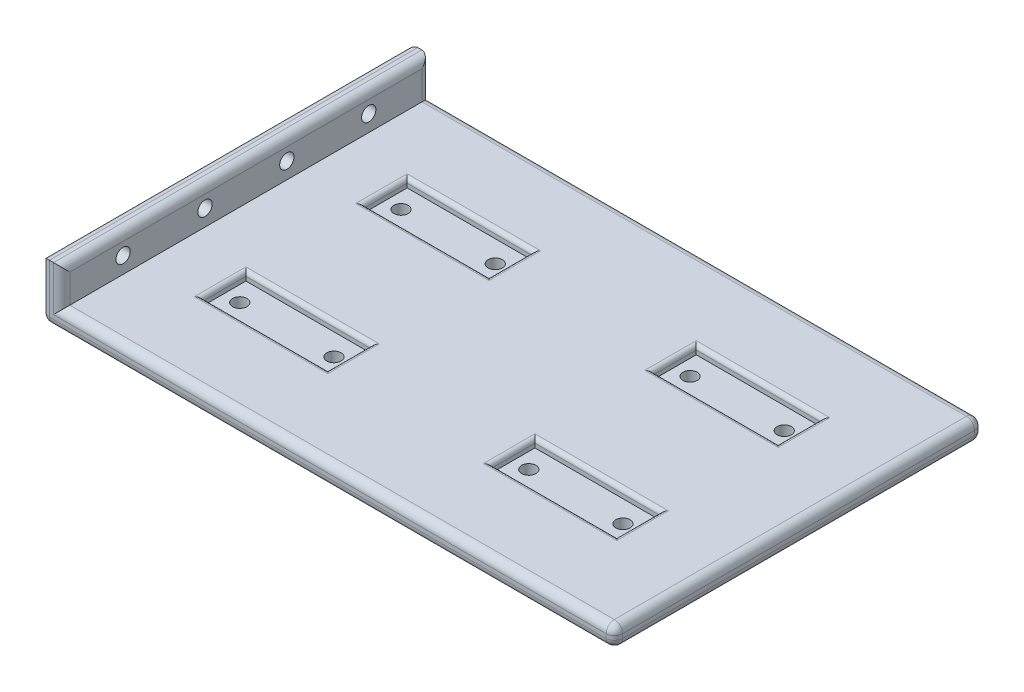
SolidWorks part; units mm, degrees
ref_plane "正面" through (0, 0, 0) normal (0, 0, 1) x (1, 0, 0)
ref_plane "平面" through (0, 0, 0) normal (0, 1, 0) x (1, 0, 0)
ref_plane "右側面" through (0, 0, 0) normal (1, 0, 0) x (0, 0, -1)
sketch "ｽｹｯﾁ1" plane through (0, 0, 0) normal (0, 1, 0) x (1, 0, 0)
  line L1 (-70, 45) -> (70, 45)
  line L2 (-70, 45) -> (-70, -45)
  line L3 (-70, -45) -> (70, -45)
  line L4 (70, 45) -> (70, -45)
  line L5 (-70, 45) -> (70, -45) construction
  line L6 (-70, -45) -> (70, 45) construction
  point P0 (0, 0)
extrude "ﾎﾞｽ - 押し出し1" add sketch "ｽｹｯﾁ1" along normal blind 5
sketch "ｽｹｯﾁ2" plane through (0, 5, 0) normal (0, 1, 0) x (1, 0, 0)
  line L1 (-70, 45) -> (-65, 45)
  line L2 (-70, 45) -> (-70, -45)
  line L3 (-70, -45) -> (-65, -45)
  line L4 (-65, 45) -> (-65, -45)
  dimension "D1" = 5
extrude "ﾎﾞｽ - 押し出し2" add sketch "ｽｹｯﾁ2" along normal blind 9
sketch "ｽｹｯﾁ3" plane through (-70, 0, 0) normal (-1, 0, 0) x (0, 0, 1)
  line L0 (-45, 14) -> (45, 14) construction
  line L1 (-45, 14) -> (-45, 0) construction
  line L2 (0, 0) -> (0, 14)
  line L3 (-45, 0) -> (45, 0) construction
  circle A0 centre (-30, 9) radius 1.75
  circle A1 centre (-10, 9) radius 1.75
  circle A2 centre (30, 9) radius 1.75
  circle A3 centre (10, 9) radius 1.75
  dimension "D2" = 3.5
  dimension "D4" = 3.5
  dimension "D1" = 5
  dimension "D3" = 15
  dimension "D5" = 20
  dimension "D6" = 5
extrude "ｶｯﾄ - 押し出し1" cut sketch "ｽｹｯﾁ3" against normal blind 11 contours A2 | A3 | A1 | A0 region at (-70, 9, -30) region at (-70, 9, -10) region at (-70, 9, 30) region at (-70, 9, 10)
sketch "ｽｹｯﾁ5" plane through (0, 5, 0) normal (0, 1, 0) x (1, 0, 0)
  line L0 (-65, -45) -> (70, -45) construction
  line L1 (-20, -25) -> (-50.6, -25)
  line L2 (-20, -25) -> (-20, -14.4)
  line L3 (-20, -14.4) -> (-50.6, -14.4)
  line L4 (-50.6, -25) -> (-50.6, -14.4)
  line L5 (-20, -19.7) -> (-50.6, -19.7) construction
  line L6 (-35.3, -25) -> (-35.3, -14.4) construction
  line L7 (70, 0) -> (0, 0) construction
  line L8 (70, -45) -> (70, 45) construction
  line L9 (0, 0) -> (-70.4783, 0) construction
  line L10 (0, 0) -> (0, 45) construction
  line L11 (70, 45) -> (-65, 45) construction
  line L12 (-35.3, 25) -> (-35.3, 14.4) construction
  line L13 (-20, 19.7) -> (-50.6, 19.7) construction
  line L14 (-50.6, 25) -> (-50.6, 14.4)
  line L15 (-20, 14.4) -> (-50.6, 14.4)
  line L16 (-20, 25) -> (-20, 14.4)
  line L17 (-20, 25) -> (-50.6, 25)
  line L18 (20, 19.7) -> (50.6, 19.7) construction
  line L19 (35.3, 25) -> (35.3, 14.4) construction
  line L20 (35.3, -25) -> (35.3, -14.4) construction
  line L21 (20, -19.7) -> (50.6, -19.7) construction
  line L22 (20, 25) -> (50.6, 25)
  line L23 (20, 25) -> (20, 14.4)
  line L24 (20, 14.4) -> (50.6, 14.4)
  line L25 (50.6, 25) -> (50.6, 14.4)
  line L26 (50.6, -25) -> (50.6, -14.4)
  line L27 (20, -14.4) -> (50.6, -14.4)
  line L28 (20, -25) -> (20, -14.4)
  line L29 (20, -25) -> (50.6, -25)
  circle A0 centre (-46.8, -19.7) radius 1.75
  circle A1 centre (-23.8, -19.7) radius 1.75
  circle A2 centre (-23.8, 19.7) radius 1.75
  circle A3 centre (-46.8, 19.7) radius 1.75
  circle A4 centre (46.8, 19.7) radius 1.75
  circle A5 centre (23.8, 19.7) radius 1.75
  circle A6 centre (23.8, -19.7) radius 1.75
  circle A7 centre (46.8, -19.7) radius 1.75
  dimension "D5" = 3.5
  dimension "D7" = 11.5
  dimension "D1" = 10.6
  dimension "D2" = 30.6
  dimension "D3" = 20
  dimension "D4" = 20
  dimension "D6" = 0
extrude "ｶｯﾄ - 押し出し2" cut sketch "ｽｹｯﾁ5" against normal blind 2
extrude "ｶｯﾄ - 押し出し3" cut sketch "ｽｹｯﾁ5<3>" against normal through all contours A7 | A6 | A4 | A5 | A2 | A1 | A0 | A3 region at (-46.8, 5, 19.7) region at (-23.8, 5, 19.7) region at (-23.8, 5, -19.7) region at (46.8, 5, -19.7) region at (23.8, 5, -19.7) region at (23.8, 5, 19.7) region at (46.8, 5, 19.7)
sketch "ｽｹｯﾁ5<3>" plane through (0, 5, 0) normal (0, 1, 0) x (1, 0, 0) same geometry as "ｽｹｯﾁ5"
fillet "ﾌｨﾚｯﾄ1" radius 2 15 edges at (70, 0, 0) (70, 5, 0) (-65, 14, 0) (-70, 14, 0) (-70, 0, 0) (0, 0, -45) (0, 0, 45) (-70, 7, 45) (-70, 7, -45) (70, 2.5, 45) (70, 2.5, -45)
fillet "ﾌｨﾚｯﾄ2" radius 1 16 edges at (20, 5, -19.7) (35.3, 5, -25) (35.3, 5, -14.4) (50.6, 5, -19.7) (50.6, 5, 19.7) (35.3, 5, 25) (20, 5, 19.7) (35.3, 5, 14.4) (-50.6, 5, -19.7) (-35.3, 5, -25) (-35.3, 5, -14.4) (-20, 5, -19.7) (-50.6, 5, 19.7) (-35.3, 5, 14.4) (-20, 5, 19.7) (-35.3, 5, 25)
